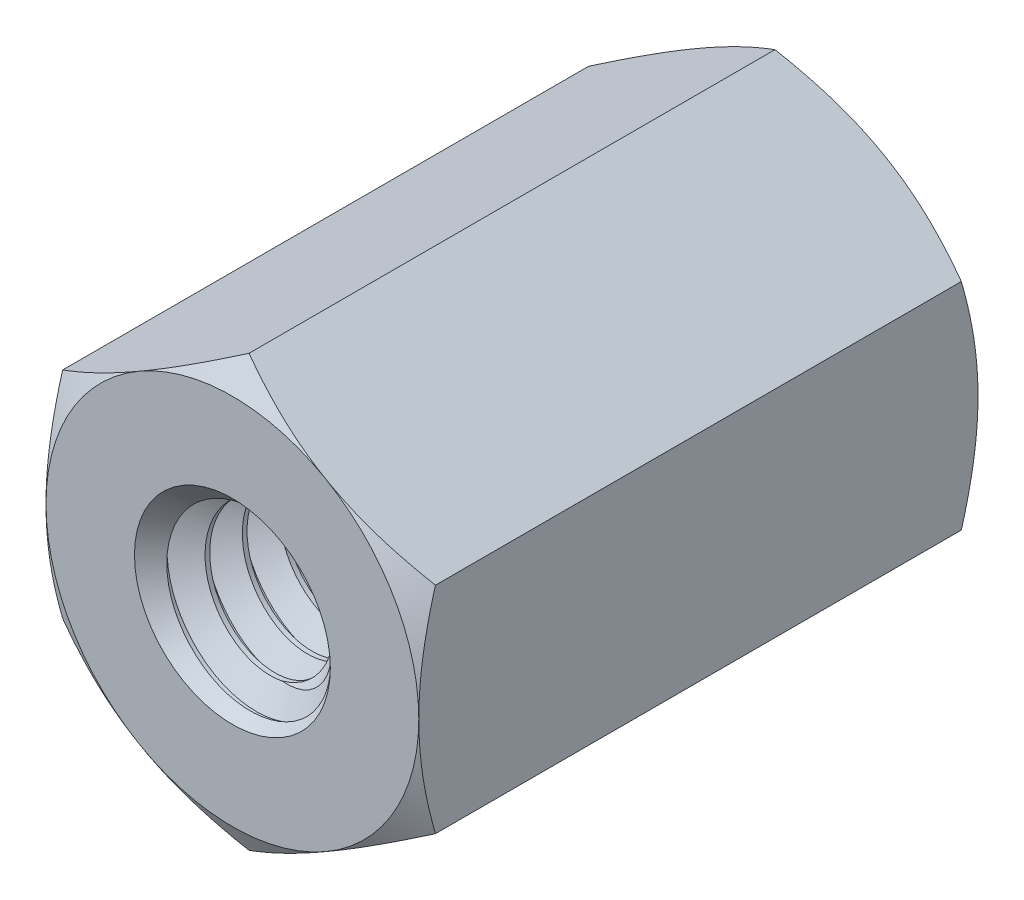
SolidWorks part; units mm, degrees
ref_plane "Front Plane" through (0, 0, 0) normal (0, 0, 1) x (1, 0, 0)
ref_plane "Top Plane" through (0, 0, 0) normal (0, 1, 0) x (1, 0, 0)
ref_plane "Right Plane" through (0, 0, 0) normal (1, 0, 0) x (0, 0, -1)
sketch "Sketch1" plane through (0, 0, 0) normal (1, 0, 0) x (0, 0, -1)
  line L0 (-3, 0) -> (3, 0) construction
  line L1 (0, 2) -> (0, -2) construction
  line L2 (-3, 1) -> (-3, -1) construction
  point P9 (3, 2)
  point P10 (-3, 2)
  dimension "Length" = 6
  dimension "Thread Dia" = 2
  dimension "Hex" = 4
sketch "Sketch19" plane through (0, 0, 0) normal (0, 0, 1) x (1, 0, 0)
  line L1 (0, 2.3094) -> (-2, 1.1547)
  line L2 (-2, 1.1547) -> (-2, -1.1547)
  line L3 (-2, -1.1547) -> (0, -2.3094)
  line L4 (0, -2.3094) -> (2, -1.1547)
  line L5 (2, -1.1547) -> (2, 1.1547)
  line L6 (2, 1.1547) -> (0, 2.3094)
  circle A0 centre (0, 0) radius 2 construction
  circle A1 centre (0, 0) radius 1
  point P10 (0, -1)
extrude "Extrude1" add sketch "Sketch19" along normal up to vertex (3 mm away) and the other way up to vertex (3 mm away) up to point (0, 0, 3) other way up to point (0, 0, -3)
sketch "Sketch8" plane through (0, 0, -3) normal (0, 0, -1) x (-1, 0, 0)
  circle A0 centre (0, 0) radius 2 construction
  circle A1 centre (0, 0) radius 2
extrude "Extrude4" cut sketch "Sketch8" against normal through all draft 60 flip side to cut
mirror "Mirror2" about plane through (0, 0, 0) normal (0, 0, 1) of "Extrude4"
sketch "Sketch11" plane through (0, 0, -3) normal (0, 0, -1) x (-1, 0, 0)
  circle A0 centre (0, 0) radius 1 construction
  circle A1 centre (0, 0) radius 1
curve "Helix/Spiral1" pitch 0.4 height 6.4 radius 1 centre (0, 0, -3) axis (0, 0, 1) start towards (0, 1, 0) parameters "Pitch"=0.4
sketch "Sketch12" plane through (0, 0, 0) normal (1, 0, 0) x (0, 0, -1)
  line L0 (3.35, 1) -> (3, 1)
  line L1 (3.35, 1) -> (3.2, 0.7402)
  line L2 (3.2, 0.7402) -> (3.15, 0.7402)
  line L3 (3.15, 0.7402) -> (3, 1)
  line L4 (3.175, 0.7402) -> (3.175, 1) construction
  line L5 (3.275, 0.8701) -> (3.075, 0.8701) construction
  dimension "D1" = 0.05
  dimension "D2" = 0.2
  dimension "D3" = 60
sweep "Sweep1" add profiles "Sketch12" path "Helix/Spiral1"
sketch "Sketch6" plane through (0, 0, -3) normal (0, 0, -1) x (-1, 0, 0)
  arc A6 (-1, 1.7321) -> (-2, 0) centre (0, 0) ccw
  arc A7 (-1, 1.7321) -> (-2, 0) centre (0, 0) ccw
  arc A8 (-2, 0) -> (-1, -1.7321) centre (0, 0) ccw
  arc A9 (-2, 0) -> (-1, -1.7321) centre (0, 0) ccw
  arc A10 (-1, -1.7321) -> (1, -1.7321) centre (0, 0) ccw
  arc A11 (-1, -1.7321) -> (1, -1.7321) centre (0, 0) ccw
  arc A12 (1, -1.7321) -> (2, 0) centre (0, 0) ccw
  arc A13 (1, -1.7321) -> (2, 0) centre (0, 0) ccw
  arc A14 (2, 0) -> (1, 1.7321) centre (0, 0) ccw
  arc A15 (2, 0) -> (1, 1.7321) centre (0, 0) ccw
  arc A16 (1, 1.7321) -> (-1, 1.7321) centre (0, 0) ccw
  arc A17 (1, 1.7321) -> (-1, 1.7321) centre (0, 0) ccw
  dimension "D1" = 0
extrude "Extrude2" cut sketch "Sketch6" along normal through all
sketch "Sketch7" plane through (0, 0, -3) normal (0, 0, -1) x (-1, 0, 0)
  circle A2 centre (0, 0) radius 1.0508
  circle A3 centre (0, 0) radius 1.0508
  dimension "D1" = 0.0508
extrude "Extrude3" cut sketch "Sketch7" against normal through all draft 43
mirror "Mirror1" about plane through (0, 0, 0) normal (0, 0, 1) of "Extrude3", "Extrude2"
equation "\"D3@Helix/Spiral1\" = \"Length@Sketch1\" + \"Pitch@Helix/Spiral1\""
equation "\"D1@Sketch12\" = \"Pitch@Helix/Spiral1\"*.125"
equation "\"D2@Sketch12\" = \"Pitch@Helix/Spiral1\"*.5"
